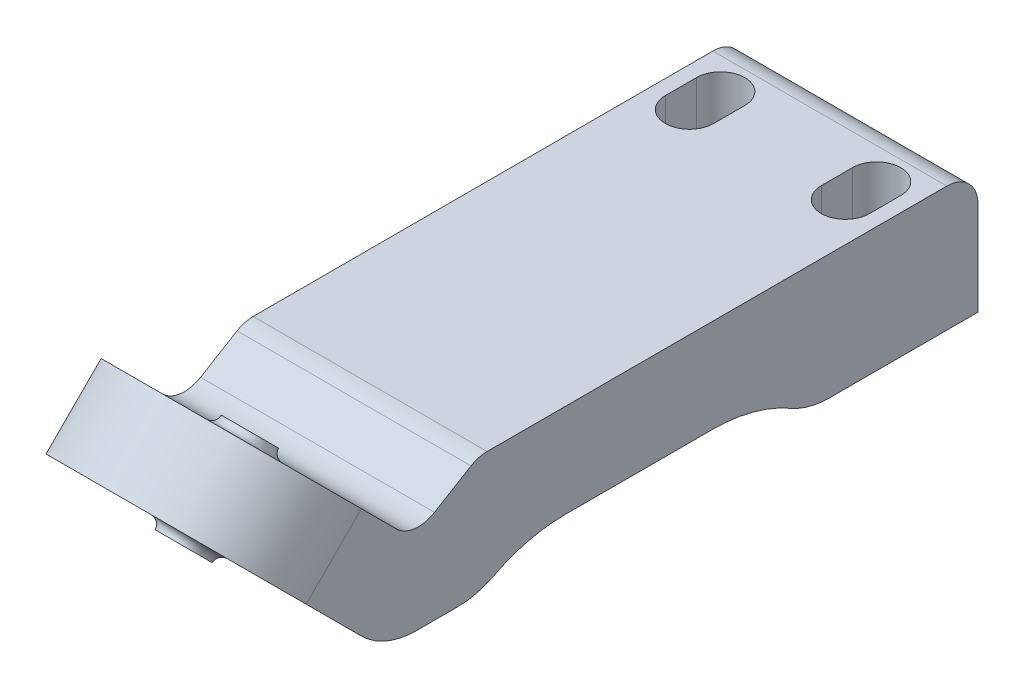
SolidWorks part; units mm, degrees
ref_plane "前视基准面" through (0, 0, 0) normal (0, 0, 1) x (1, 0, 0)
ref_plane "上视基准面" through (0, 0, 0) normal (0, 1, 0) x (1, 0, 0)
ref_plane "右视基准面" through (0, 0, 0) normal (1, 0, 0) x (0, 0, -1)
other "Configuration Table"
sketch "草图10" plane through (0, 0, 0) normal (0, 0, 1) x (1, 0, 0)
  line L0 (-7.5, 20.6821) -> (7.5, 20.6821) construction
  line L1 (-7.5, 20.6821) -> (7.5, 20.6821)
  line L2 (7.5, 20.6821) -> (7.5, 28.6821)
  line L3 (7.5, 28.6821) -> (-7.5, 28.6821)
  line L4 (-7.5, 28.6821) -> (-7.5, 20.6821)
  arc A0 (-7.5, 20.6821) -> (7.5, 20.6821) centre (0, 0) ccw construction
  dimension "D1" = 44
  dimension "D2" = 15
  dimension "D3" = 8
extrude "凸台-拉伸7" add sketch "草图10" along normal blind 26
sketch "草图11" plane through (0, 28.6821, 0) normal (0, 1, 0) x (1, 0, 0)
  line L0 (0, 3.3102) -> (0, -13.8287) construction
  line L1 (-5, -4) -> (-5, -6) construction
  line L2 (-3.45, -4) -> (-3.45, -6)
  line L3 (-6.55, -4) -> (-6.55, -6)
  line L5 (5, -4) -> (5, -6) construction
  line L6 (3.45, -4) -> (3.45, -6)
  line L7 (6.55, -4) -> (6.55, -6)
  line L8 (7.5, 0) -> (-7.5, 0) construction
  arc A0 (-3.45, -4) -> (-6.55, -4) centre (-5, -4) ccw
  arc A1 (-6.55, -6) -> (-3.45, -6) centre (-5, -6) ccw
  arc A2 (3.45, -4) -> (6.55, -4) centre (5, -4) cw
  arc A3 (6.55, -6) -> (3.45, -6) centre (5, -6) cw
  point P5 (-5, -5)
  point P14 (5, -5)
  dimension "D2" = 1.55
  dimension "D1" = 5
  dimension "D3" = 2
  dimension "D4" = 10
extrude "切除-拉伸4" cut sketch "草图11" against normal blind 11
sketch "草图12" plane through (0, 0, 26) normal (0, 0, 1) x (1, 0, 0)
  line L0 (7.5, 20.6821) -> (7.5, 28.6821) construction
  line L1 (-7.5, 28.6821) -> (7.5, 28.6821)
  line L2 (-7.5, 28.6821) -> (-7.5, 22.6821)
  line L3 (-7.5, 22.6821) -> (7.5, 22.6821)
  line L4 (7.5, 28.6821) -> (7.5, 22.6821)
  dimension "D1" = 6
extrude "凸台-拉伸8" add sketch "草图12" along normal blind 6
sketch "草图14" plane through (0, 0, 32) normal (0, 0, 1) x (1, 0, 0)
  line L0 (-7.5, 20.6821) -> (7.5, 20.6821) construction
  line L1 (0, 26) -> (-20.4245, 26) construction
  line L2 (-7.5, 26) -> (7.5, 26)
  line L3 (7.5, 26) -> (7.5, 21)
  line L4 (7.5, 20.6821) -> (7.5, 22.6821) construction
  line L5 (7.5, 21) -> (-7.5, 21)
  line L6 (-7.5, 22.6821) -> (-7.5, 20.6821) construction
  line L7 (-7.5, 21) -> (-7.5, 26)
  line L8 (-7.5, 28.6821) -> (-7.5, 22.6821) construction
  arc A0 (-7.5, 20.6821) -> (7.5, 20.6821) centre (0, 0) ccw construction
  circle A1 centre (0, 0) radius 26 construction
  dimension "D1" = 52
  dimension "D2" = 5
extrude "凸台-拉伸9" add sketch "草图14" along normal blind 4
sketch "草图17" plane through (-7.5, 0, 0) normal (-1, 0, 0) x (0, 0, 1)
  line L0 (36, 26) -> (39.5355, 29.5355)
  line L1 (36, 26) -> (32, 26) construction
  line L2 (43.0711, 26) -> (38.0711, 21)
  line L4 (39.5355, 29.5355) -> (43.0711, 26)
  line L5 (36, 26) -> (36, 21)
  line L6 (36, 21) -> (38.0711, 21)
  dimension "D1" = 135
  dimension "D2" = 5
  dimension "D3" = 5
extrude "凸台-拉伸10" add sketch "草图17" against normal blind 15
sketch "草图18" plane through (0, -8.5355, 8.5355) normal (0, -0.7071, 0.7071) x (1, 0, 0)
  line L0 (7.5, 48.8406) -> (-7.5, 48.8406) construction
  line L1 (7.5, 41.7696) -> (7.5, 48.8406) construction
  line L2 (7.5, 48.8406) -> (-7.5, 48.8406)
  arc A0 (-7.5, 48.8406) -> (7.5, 48.8406) centre (0, 48.8406) cw
extrude "凸台-拉伸11" add sketch "草图18" against normal blind 5
sketch "草图19" plane through (0, -8.5355, 8.5355) normal (0, -0.7071, 0.7071) x (1, 0, 0)
  circle A0 centre (0, 48.8406) radius 1.1
  dimension "D1" = 2.2
extrude "切除-拉伸5" cut sketch "草图19" against normal blind 5
sketch "草图20" plane through (0, -8.5355, 8.5355) normal (0, -0.7071, 0.7071) x (1, 0, 0)
  circle A0 centre (0, 48.8406) radius 1.1 construction
  circle A1 centre (0, 48.8406) radius 1.1
  circle A2 centre (0, 48.8406) radius 1.5
  dimension "D1" = 3
extrude "凸台-拉伸12" add sketch "草图20" along normal blind 0.5
sketch "草图21" plane through (0, -5, 5) normal (0, 0.7071, -0.7071) x (1, 0, 0)
  circle A0 centre (0, -48.8406) radius 1.1 construction
  circle A1 centre (0, -48.8406) radius 1.1
  circle A2 centre (0, -48.8406) radius 1.5
  dimension "D1" = 3
extrude "凸台-拉伸13" add sketch "草图21" along normal blind 0.5
fillet "圆角4" radius 0.5 2 edges at (0, 24.9393, 42.0104) (0, 30.5962, 40.5962)
chamfer "倒角1" distance 2.7 angle 59 1 edges at (0, 26, 32) first distance on face at (0, 27.3411, 32)
fillet "圆角7" radius 2 2 edges at (0, 28.6821, 32.0298) (0, 26.1852, 36.1852)
sketch "草图22" plane through (0, 0, 26) normal (0, 0, 1) x (1, 0, 0)
  line L4 (7.5, 22.6821) -> (-7.5, 22.6821)
  line L5 (-7.5, 22.6821) -> (-7.5, 20.6821)
  line L6 (-7.5, 20.6821) -> (7.5, 20.6821)
  line L7 (7.5, 20.6821) -> (7.5, 22.6821)
  line L8 (7.5, 22.6821) -> (-7.5, 22.6821)
  line L9 (-7.5, 22.6821) -> (-7.5, 20.6821)
  line L10 (-7.5, 20.6821) -> (7.5, 20.6821)
  line L11 (7.5, 20.6821) -> (7.5, 22.6821)
  dimension "D1" = 0
extrude "切除-拉伸6" cut sketch "草图22" against normal blind 15
fillet "圆角8" radius 10 2 edges at (0, 22.6821, 11) (0, 22.6821, 32)
fillet "圆角9" radius 5 3 edges at (0, 20.6821, 11) (0, 21, 38.0711) (0, 21, 32)
fillet "圆角10" radius 2 1 edges at (0, 28.6821, 0)
